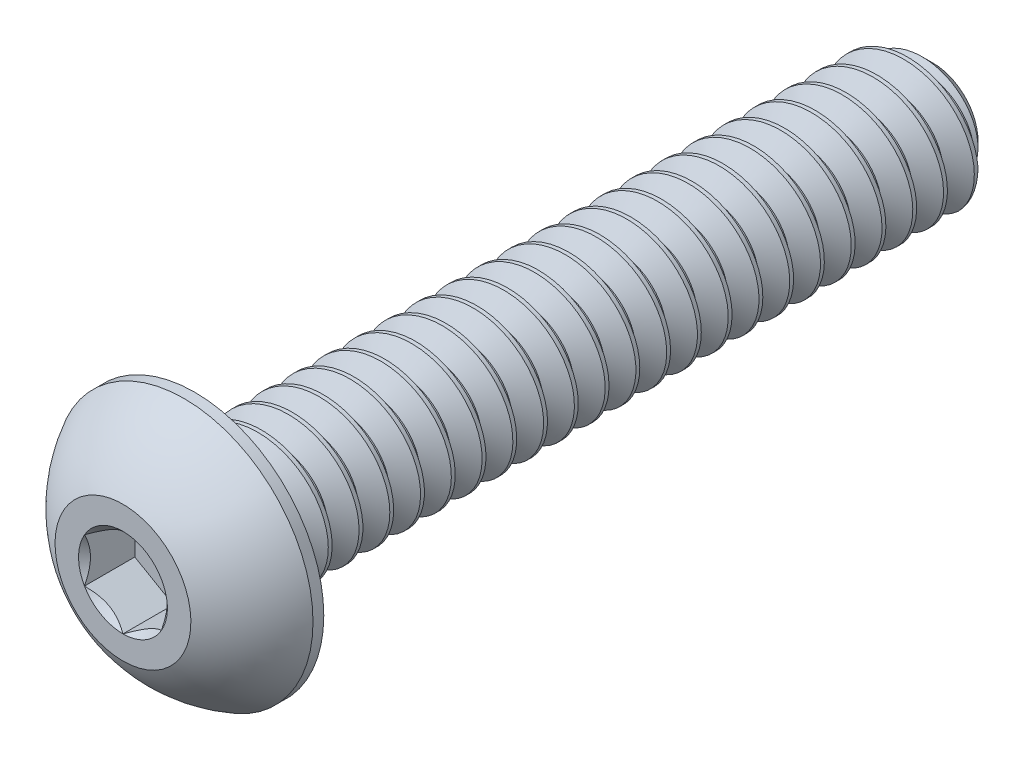
SolidWorks part; units mm, degrees
material "1023 Carbon Steel Sheet (SS)"
ref_plane "Front" through (0, 0, 0) normal (0, 0, 1) x (1, 0, 0)
ref_plane "Top" through (0, 0, 0) normal (0, 1, 0) x (1, 0, 0)
ref_plane "Right" through (0, 0, 0) normal (1, 0, 0) x (0, 0, -1)
sketch "Sketch1" plane through (0, 0, 0) normal (1, 0, 0) x (0, 0, -1)
  line L2 (1.8542, 1.7526) -> (20.9042, 1.7526)
  line L3 (20.9042, 1.7526) -> (20.9042, 0)
  line L4 (20.9042, 0) -> (1.8542, 0)
  line L6 (1.5761, 3.3274) -> (1.8542, 3.3274) construction
  line L7 (20.9042, 1.7526) -> (20.9042, -1.7526) construction
  line L8 (0, 0) -> (1.8542, 0) construction
  line L9 (1.8542, 3.3274) -> (1.8542, -3.3274) construction
  line L11 (1.8542, 1.7526) -> (1.8542, 0)
  line L13 (0, 0.9922) -> (0, -0.9922) construction
  line L14 (0, 0.9922) -> (0, 1.7526) construction
  arc A3 (0, 1.7526) -> (1.5761, 3.3274) centre (3.326, 0) cw construction
  dimension "D1" = 0.2781
revolve "Revolve1" add sketch "Sketch1" angle 360 mid plane about L4
sketch "Sketch3" plane through (0, 0, -20.9042) normal (0, 0, -1) x (-1, 0, 0)
  circle A0 centre (0, 0) radius 1.7526
curve "Helix/Spiral1" pitch 0.7937 height 19.8438 turns 25
sketch "Sketch2" plane through (0, 0, 0) normal (1, 0, 0) x (0, 0, -1)
  line L0 (20.9042, 1.7526) -> (21.5987, 1.7526)
  line L1 (21.5987, 1.7526) -> (21.3011, 1.237)
  line L2 (21.3011, 1.237) -> (21.2019, 1.237)
  line L3 (21.2019, 1.237) -> (20.9042, 1.7526)
  line L4 (21.053, 1.4948) -> (21.4499, 1.4948) construction
  dimension "D1" = 60
  dimension "D2" = 0.0992
  dimension "D3" = 0.3969
chamfer "Chamfer1" distance 0.5953 angle 45 1 edges at (0, 1.7526, -20.9042)
sweep "Cut-Sweep1" cut profiles "Sketch2" path "Helix/Spiral1"
sketch "Sketch7" plane through (0, 0, 0) normal (1, 0, 0) x (0, 0, -1)
  line L6 (1.5761, 3.3274) -> (1.8542, 3.3274) construction
  line L8 (0, 0) -> (1.8542, 0) construction
  line L11 (1.8542, 3.3274) -> (1.8542, -3.3274) construction
  line L12 (1.5761, 3.3274) -> (1.8542, 3.3274)
  line L13 (0, 0) -> (1.8542, 0)
  line L14 (0, 0.9922) -> (0, -0.9922) construction
  line L15 (1.8542, 3.3274) -> (1.8542, 0)
  line L16 (0, 1.7526) -> (0, 0)
  arc A2 (1.5761, 3.3274) -> (0, 1.7526) centre (3.326, 0) ccw construction
  arc A3 (1.5761, 3.3274) -> (0, 1.7526) centre (3.326, 0) ccw
revolve "Revolve2" add sketch "Sketch7" angle 360 mid plane about L13
sketch "Sketch5" plane through (0, 0, 0) normal (0, 0, 1) x (1, 0, 0)
  line L1 (0.9922, -0.5728) -> (0.9922, 0.5728)
  line L2 (0.9922, 0.5728) -> (0, 1.1457)
  line L3 (0, 1.1457) -> (-0.9922, 0.5728)
  line L4 (-0.9922, 0.5728) -> (-0.9922, -0.5728)
  line L5 (-0.9922, -0.5728) -> (0, -1.1457)
  line L6 (0, -1.1457) -> (0.9922, -0.5728)
  circle A0 centre (0, 0) radius 0.9922 construction
extrude "Cut-Extrude2" cut sketch "Sketch5" against normal blind 1.2979
sketch "Sketch6" plane through (0, 0, 0) normal (0, 0, 1) x (1, 0, 0)
  circle A0 centre (0, 0) radius 1.1457
extrude "Cut-Extrude3" cut sketch "Sketch6" against normal blind 1.2979 draft 45
sketch "Sketch9" [suppressed] plane through (0, 0, -1.8542) normal (0, 0, 1) x (1, 0, 0)
  circle A2 centre (0, 0) radius 1.7526
extrude "Boss-Extrude2" [suppressed] add sketch "Sketch9" against normal offset from surface (6.35 mm away) 28.575
sketch "Sketch10" plane through (0, 0, 0) normal (1, 0, 0) x (0, 0, -1)
  line L0 (20.9042, 1.7526) -> (20.9042, -1.7526) construction
  point P0 (19.7136, -1.7526)
  dimension "D1" = 1.1906
equation "\"D3@Helix/Spiral1\" = \"Lg@Sketch1\" + \"D4@Helix/Spiral1\""
equation "\"D2@Sketch2\" = \"D4@Helix/Spiral1\" * .125"
equation "\"D3@Sketch2\" = \"D4@Helix/Spiral1\" * .5"
equation "\"D1@Chamfer1\" = \"D4@Helix/Spiral1\" * .75"
equation "\"D1@Cut-Extrude2\" = \"Head Ht@Sketch1\" * .7"
equation "\"D1@Sketch1\" = \"Head Ht@Sketch1\" * .15"
equation "\"D1@Sketch10\" = \"D4@Helix/Spiral1\" * 1.5"
equation "\"D1@Cut-Extrude3\" = \"D1@Cut-Extrude2\""
